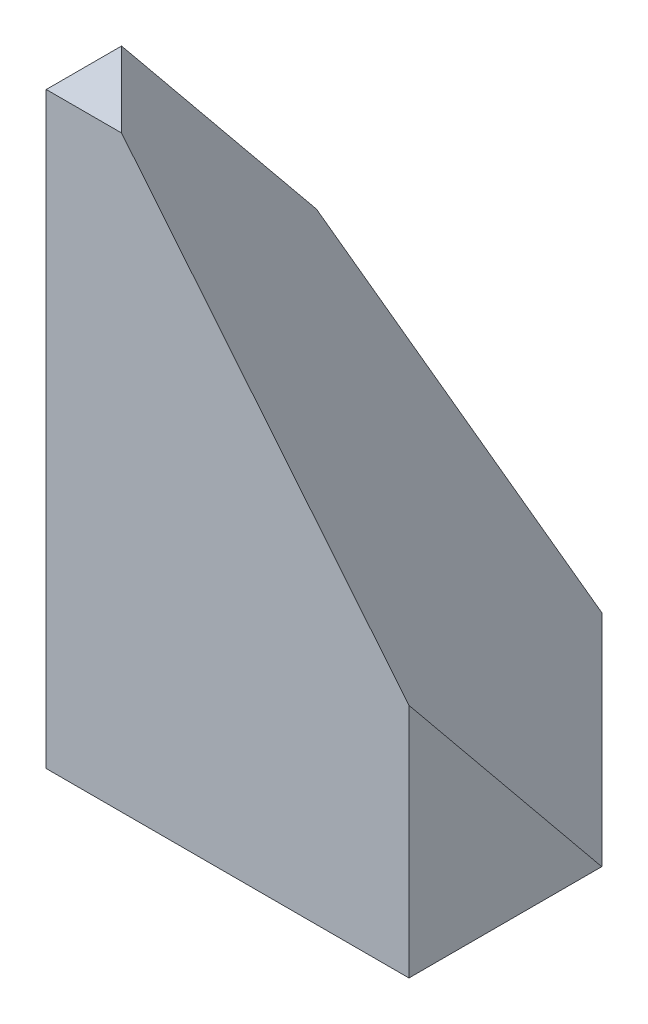
SolidWorks part; units mm, degrees
ref_plane "Front Plane" through (0, 0, 0) normal (0, 0, 1) x (1, 0, 0)
ref_plane "Top Plane" through (0, 0, 0) normal (0, 1, 0) x (1, 0, 0)
ref_plane "Right Plane" through (0, 0, 0) normal (1, 0, 0) x (0, 0, -1)
sketch "Sketch1" plane through (0, 0, 0) normal (0, 1, 0) x (1, 0, 0)
  line L0 (0, 0) -> (0, 16)
  line L2 (14, 0) -> (0, 0)
  line L3 (0, 16) -> (14, 16)
  line L4 (14, 16) -> (14, 0)
  dimension "D1" = 14
  dimension "D2" = 16
extrude "Boss-Extrude1" add sketch "Sketch1" along normal blind 22.7
ref_plane "Plane1" through (8.0404, 6.565, -8.0404) normal (-0.6124, -0.5, 0.6124) x (0.7906, -0.3873, 0.4743)
sketch "Sketch2" plane through (8.0404, 6.565, -8.0404) normal (-0.6124, -0.5, 0.6124) x (0.7906, -0.3873, 0.4743)
  line L1 (25.0062, -28.8765) -> (-25.0062, -28.8765)
  line L2 (25.0062, -28.8765) -> (25.0062, 28.8765)
  line L3 (25.0062, 28.8765) -> (-25.0062, 28.8765)
  line L4 (-25.0062, -28.8765) -> (-25.0062, 28.8765)
  line L5 (25.0062, -28.8765) -> (-25.0062, 28.8765) construction
  line L6 (25.0062, 28.8765) -> (-25.0062, -28.8765) construction
  point P0 (0, 0)
extrude "Cut-Extrude1" cut sketch "Sketch2" against normal through all
ref_plane "Plane2" through (-5.2147, 0, -5.2147) normal (-0.7071, 0, -0.7071) x (-0.7071, 0, 0.7071)
sketch "Sketch3" plane through (-5.2147, 0, -5.2147) normal (-0.7071, 0, -0.7071) x (-0.7071, 0, 0.7071)
  line L1 (-33.5779, 52.022) -> (18.3363, 52.022)
  line L2 (-33.5779, 52.022) -> (-33.5779, -25.8514)
  line L3 (-33.5779, -25.8514) -> (18.3363, -25.8514)
  line L4 (18.3363, 52.022) -> (18.3363, -25.8514)
  line L5 (-33.5779, 52.022) -> (18.3363, -25.8514) construction
  line L6 (-33.5779, -25.8514) -> (18.3363, 52.022) construction
  point P0 (-7.6208, 13.0853)
extrude "Cut-Extrude2" cut sketch "Sketch3" along normal through all
